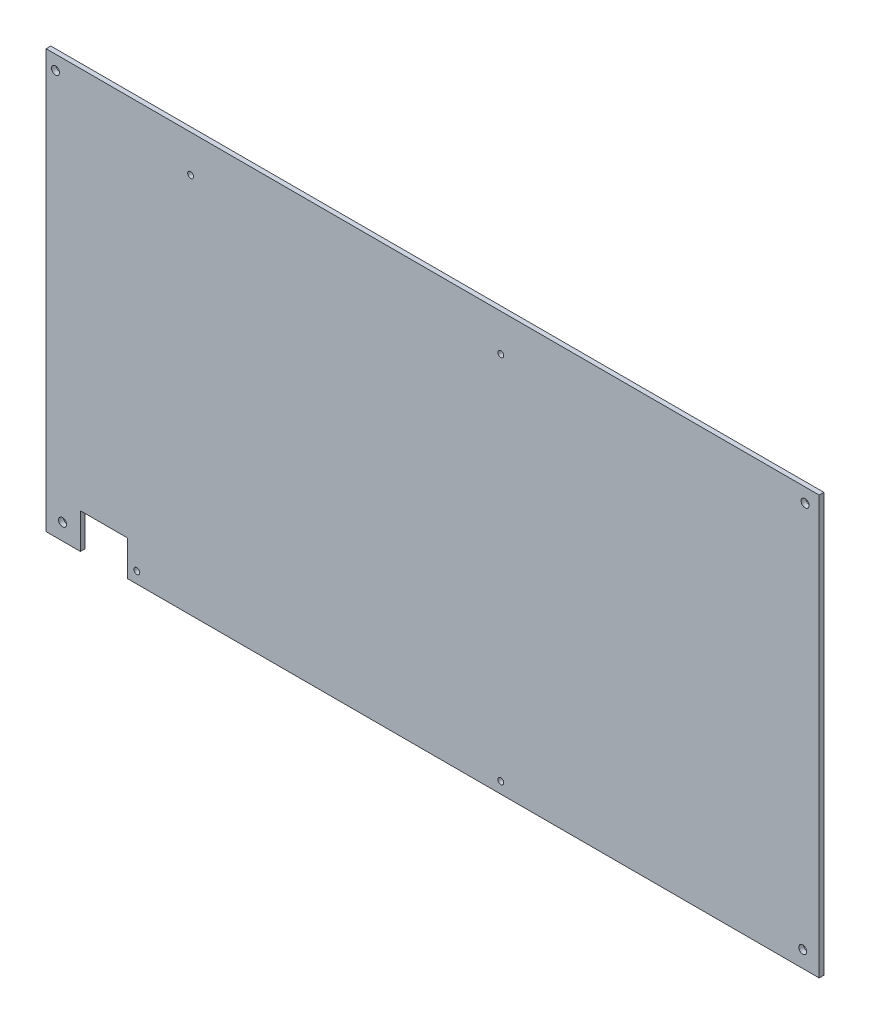
SolidWorks part; units mm, degrees
material "5052-H38"
ref_plane "Front" through (0, 0, 0) normal (0, 0, 1) x (1, 0, 0)
ref_plane "Top" through (0, 0, 0) normal (0, 1, 0) x (1, 0, 0)
ref_plane "Right" through (0, 0, 0) normal (1, 0, 0) x (0, 0, -1)
sketch "ｽｹｯﾁ1" plane through (0, 0, 0) normal (0, 0, 1) x (1, 0, 0)
  line L1 (0, 0) -> (329, 0)
  line L2 (0, 0) -> (0, 178)
  line L3 (0, 178) -> (329, 178)
  line L4 (329, 0) -> (329, 178)
  dimension "D1" = 178
  dimension "D2" = 329
base flange "ﾍﾞｰｽ-ﾌﾗﾝｼﾞ1" sketch "ｽｹｯﾁ1" thickness 2 reverse thickness direction no parameters "D1"=0.7366
hole_wizard "M3 すきま穴3" positions "ｽｹｯﾁ17" profile "ｽｹｯﾁ16" hole size "M3" standard "JIS" end condition up to next
sketch "ｽｹｯﾁ17" plane through (0, 0, 0) normal (0, 0, 1) x (1, 0, 0)
  line L0 (0, 178) -> (0, 0) construction
  line L1 (329, 0) -> (329, 178) construction
  line L2 (329, 178) -> (0, 178) construction
  point P0 (322, 7)
  point P2 (7, 7)
  point P4 (4, 172)
  point P6 (323, 172)
  dimension "D1" = 7
  dimension "D2" = 7
  dimension "D3" = 4
  dimension "D4" = 6
  dimension "D5" = 6
  dimension "D6" = 165
sketch "ｽｹｯﾁ16" plane through (322, 7, 0) normal (1, 0, 0) x (0, -1, 0)
  line L0 (0, 0) -> (0, 2)
  line L1 (0, 2) -> (1.7, 2)
  line L2 (1.7, 2) -> (1.7, 0)
  line L5 (1.7, 0) -> (0, 0)
  line L11 (0, -6.35) -> (0, 107.95) construction
  dimension "通し穴の直径" = 3.4
  dimension "通し穴の深さ" = 2
hole_wizard "M3 ねじ穴1" positions "ｽｹｯﾁ19" profile "ｽｹｯﾁ18" tap size "M3" standard "ISO" end condition up to next
sketch "ｽｹｯﾁ19" plane through (0, 0, 0) normal (0, 0, 1) x (1, 0, 0)
  line L0 (0, 178) -> (0, 0) construction
  line L1 (329, 178) -> (0, 178) construction
  point P0 (61.5, 162.2)
  point P2 (193.5, 162.2)
  point P4 (193.5, 4.8)
  point P6 (38.6, 4.8)
  dimension "D1" = 132
  dimension "D2" = 154.9
  dimension "D3" = 61.5
  dimension "D4" = 22.9
  dimension "D5" = 157.4
  dimension "D6" = 15.8
cosmetic thread "穴のねじ山5"
cosmetic thread "穴のねじ山6"
cosmetic thread "穴のねじ山7"
cosmetic thread "穴のねじ山8"
sketch "ｽｹｯﾁ18" plane through (61.5, 162.2, 0) normal (1, 0, 0) x (0, -1, 0)
  line L0 (0, 0) -> (0, 2)
  line L1 (0, 2) -> (1.25, 2)
  line L2 (1.25, 2) -> (1.25, 0)
  line L5 (1.25, 0) -> (0, 0)
  line L11 (0, -6.35) -> (0, 107.95) construction
  dimension "次ｻｰﾌｪｽまでのねじ下穴ﾄﾞﾘﾙ直径" = 2.5
  dimension "次ｻｰﾌｪｽまでのねじ下穴ﾄﾞﾘﾙの深さ" = 2
sketch "ｽｹｯﾁ20" plane through (0, 0, 0) normal (0, 0, 1) x (1, 0, 0)
  line L0 (0, 0) -> (329, 0) construction
  line L1 (14.6, 15) -> (34.6, 15)
  line L2 (14.6, 15) -> (14.6, 0)
  line L3 (14.6, 0) -> (34.6, 0)
  line L4 (34.6, 15) -> (34.6, 0)
  circle A0 centre (38.6, 4.8) radius 1.25 construction
  dimension "D3" = 4
  dimension "D1" = 20
  dimension "D2" = 15
extrude "ｶｯﾄ - 押し出し1" cut sketch "ｽｹｯﾁ20" against normal blind 10 normal cut yes
sketch "ﾍﾞﾝﾄﾞ-ﾗｲﾝ1" [suppressed] plane through (0, 0, 0) normal (0, 1, 0) x (1, 0, 0)
sketch "境界ﾎﾞｯｸｽ1" [suppressed] plane through (0, 0, 0) normal (0, 1, 0) x (1, 0, 0)
sheet metal parameters "板金1" thickness 2 parameters "D1"=0.7366
flat pattern "ﾌﾗｯﾄ-ﾊﾟﾀｰﾝ1" [suppressed]
sketch "ﾍﾞﾝﾄﾞ-ﾗｲﾝ2" plane through (0, 0, 0) normal (0, 1, 0) x (1, 0, 0)
sketch3d "境界ﾎﾞｯｸｽ2" [suppressed]
  line L0 (0, 0, 0) -> (329, 0, 0) construction
  line L1 (0, 175, 0) -> (329, 175, 0) construction
  line L2 (0, 0, 0) -> (0, 175, 0) construction
  line L3 (329, 0, 0) -> (329, 175, 0) construction
sheet metal parameters "板金5" thickness 2 parameters "D1"=0.7366
flat pattern "ﾌﾗｯﾄ-ﾊﾟﾀｰﾝ1"
sketch "ﾍﾞﾝﾄﾞ-ﾗｲﾝ2" plane through (0, 0, 0) normal (0, 1, 0) x (1, 0, 0)
sketch3d "境界ﾎﾞｯｸｽ2" [suppressed]
  line L0 (0, 0, 0) -> (329, 0, 0) construction
  line L1 (0, 175, 0) -> (329, 175, 0) construction
  line L2 (0, 0, 0) -> (0, 175, 0) construction
  line L3 (329, 0, 0) -> (329, 175, 0) construction
sheet metal parameters "板金6" thickness 2 parameters "D1"=0.7366
flat pattern "ﾌﾗｯﾄ-ﾊﾟﾀｰﾝ1"
sketch "ﾍﾞﾝﾄﾞ-ﾗｲﾝ2" plane through (0, 0, 0) normal (0, 1, 0) x (1, 0, 0)
sketch3d "境界ﾎﾞｯｸｽ2" [suppressed]
  line L0 (0, 0, 0) -> (329, 0, 0) construction
  line L1 (0, 178, 0) -> (329, 178, 0) construction
  line L2 (0, 0, 0) -> (0, 178, 0) construction
  line L3 (329, 0, 0) -> (329, 178, 0) construction
sheet metal parameters "板金7" thickness 2 parameters "D1"=0.7366
flat pattern "ﾌﾗｯﾄ-ﾊﾟﾀｰﾝ1"
sketch "ﾍﾞﾝﾄﾞ-ﾗｲﾝ2" plane through (0, 0, 0) normal (0, 1, 0) x (1, 0, 0)
sketch3d "境界ﾎﾞｯｸｽ2" [suppressed]
  line L0 (0, 0, 0) -> (329, 0, 0) construction
  line L1 (0, 178, 0) -> (329, 178, 0) construction
  line L2 (0, 0, 0) -> (0, 178, 0) construction
  line L3 (329, 0, 0) -> (329, 178, 0) construction
